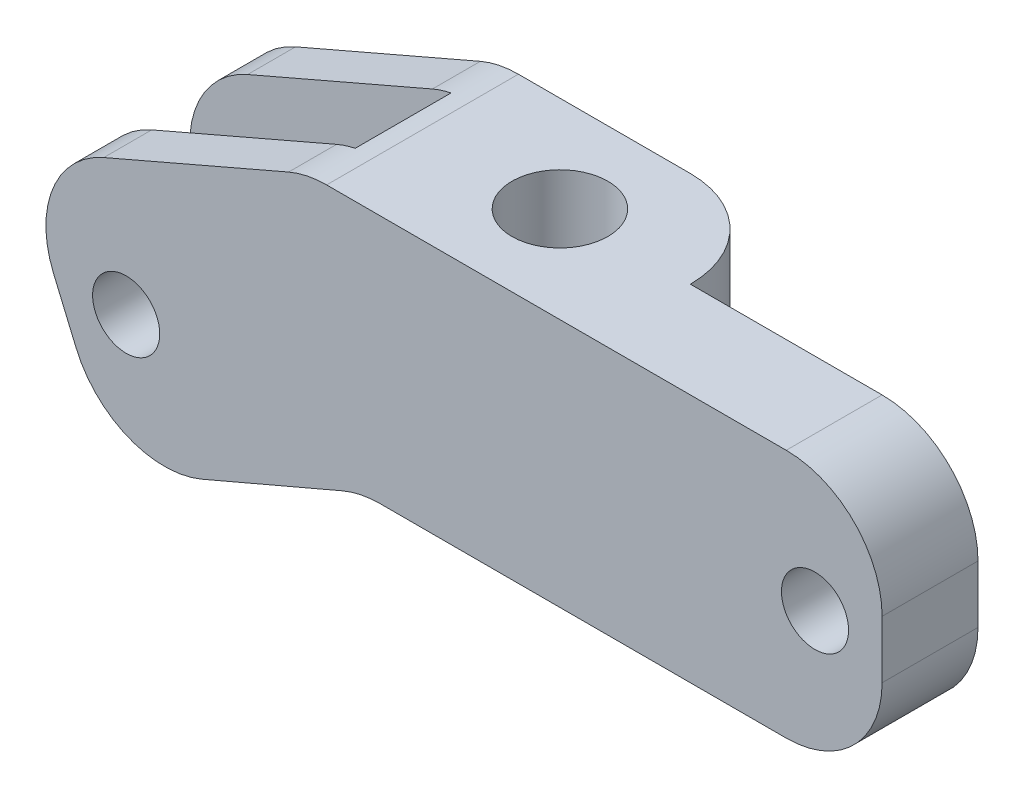
SolidWorks part; units mm, degrees
ref_plane "정면" through (0, 0, 0) normal (0, 0, 1) x (1, 0, 0)
ref_plane "윗면" through (0, 0, 0) normal (0, 1, 0) x (1, 0, 0)
ref_plane "우측면" through (0, 0, 0) normal (1, 0, 0) x (0, 0, -1)
sketch "스케치1" plane through (0, 0, 0) normal (0, 0, 1) x (1, 0, 0)
  line L0 (-6.9042, 6.5443) -> (-22.0507, -0.0005)
  line L1 (-22.0507, -0.0005) -> (-16.9734, -11.9679)
  line L2 (-4.1042, -6.4557) -> (-16.9734, -11.9679)
  line L3 (-4.1042, -6.4557) -> (23.0958, -6.4557)
  line L4 (23.0958, -6.4557) -> (23.0958, 6.5443)
  line L5 (-6.9042, 6.5443) -> (23.0958, 6.5443)
  line L6 (-19.5121, -5.9842) -> (8.0958, 6.5443) construction
  line L7 (23.0958, 0.0443) -> (-21.9471, 0.0443) construction
  circle A0 centre (-16.3239, -4.5374) radius 1.75
  circle A1 centre (19.5958, 0.0443) radius 1.75
  point P0 (-6.9042, 6.5443)
  point P1 (-4.1042, -6.4557)
  point P3 (0.0958, 0.0443)
  dimension "D9" = 3.5
  dimension "D10" = 3.5
  dimension "D1" = 13
  dimension "D2" = 30
  dimension "D3" = 27.2
  dimension "D4" = 16.5
  dimension "D5" = 14
  dimension "D6" = 13
  dimension "D7" = 3.5
  dimension "D8" = 3.5
extrude "보스-돌출1" add sketch "스케치1" along normal blind 10
ref_plane "평면1" through (0, 0, 5) normal (0, 0, 1) x (1, 0, 0)
sketch "스케치5" plane through (0, 0, 5) normal (0, 0, 1) x (1, 0, 0)
  line L0 (-6.9042, 6.5443) -> (23.0958, 6.5443)
  line L1 (23.0958, 6.5443) -> (23.1099, 6.5686)
  line L2 (-19.5121, -5.9842) -> (8.0958, 6.5443) construction
  line L3 (-22.0507, -0.0005) -> (23.0958, 0.0443) construction
  line L4 (8.0958, 6.5443) -> (8.0958, -6.4557)
  line L5 (-6.9042, 6.5443) -> (-4.1042, -6.4557)
  line L8 (-22.0507, -0.0005) -> (-16.9734, -11.9679)
  line L9 (-16.9734, -11.9679) -> (-4.1042, -6.4557)
  line L10 (-4.1042, -6.4557) -> (23.0958, -6.4557)
  line L11 (23.0958, -6.4557) -> (23.0958, 6.5443)
  line L13 (-6.9042, 6.5443) -> (-22.0507, -0.0005)
  circle A0 centre (-16.3239, -4.5374) radius 1.75
  circle A1 centre (19.5958, 0.0443) radius 1.75
  dimension "D1" = 35.9197
sketch "스케치7" plane through (0, 0, 5) normal (0, 0, 1) x (1, 0, 0)
  line L0 (-22.0507, -0.0005) -> (-6.9042, 6.5443)
  line L1 (-6.9042, 6.5443) -> (-4.1042, -6.4557)
  line L2 (-4.1042, -6.4557) -> (-16.9734, -11.9679)
  line L3 (-16.9734, -11.9679) -> (-22.0507, -0.0005)
  line L4 (-22.0507, -0.0005) -> (-22.0505, -0.001)
sketch "스케치8" plane through (0, 0, 5) normal (0, 0, 1) x (1, 0, 0)
  line L0 (-22.0507, -0.0005) -> (-6.9042, 6.5443)
  line L1 (-6.9042, 6.5443) -> (-4.1042, -6.4557)
  line L2 (-4.1042, -6.4557) -> (-16.9734, -11.9679)
  line L3 (-16.9734, -11.9679) -> (-22.0507, -0.0005)
fillet "필렛8" radius 5 6 edges at (-16.9734, -11.9679, 5) (-4.1042, -6.4557, 5) (23.0958, -6.4557, 5) (23.0958, 6.5443, 5) (-22.0507, -0.0005, 5) (-6.9042, 6.5443, 5)
sketch "스케치9" plane through (0, 0, 5) normal (0, 0, 1) x (1, 0, 0)
  line L0 (-22.0507, -0.0005) -> (-6.9042, 6.5443)
  line L1 (-6.9042, 6.5443) -> (-4.1042, -6.4557)
  line L2 (-4.1042, -6.4557) -> (-16.9734, -11.9679)
  line L3 (-16.9734, -11.9679) -> (-22.0507, -0.0005)
extrude "컷-돌출7" cut sketch "스케치9" against normal blind 2.5
sketch "스케치10" plane through (0, 0, 5) normal (0, 0, 1) x (1, 0, 0)
  line L0 (-22.0507, -0.0005) -> (-6.9042, 6.5443)
  line L1 (-6.9042, 6.5443) -> (-4.1042, -6.4557)
  line L2 (-4.1042, -6.4557) -> (-16.9734, -11.9679)
  line L3 (-16.9734, -11.9679) -> (-22.0507, -0.0005)
extrude "컷-돌출8" cut sketch "스케치10" along normal blind 2.5
sketch "스케치11" plane through (0, 0, 5) normal (0, 0, 1) x (1, 0, 0)
  line L0 (8.0958, 6.5443) -> (23.1099, 6.5686)
  line L1 (23.1099, 6.5686) -> (23.0958, -6.4557)
  line L2 (23.0958, -6.4557) -> (8.0958, -6.4557)
  line L3 (8.0958, -6.4557) -> (8.0958, 6.5443)
extrude "컷-돌출9" cut sketch "스케치11" against normal blind 5
fillet "필렛10" radius 5 1 edges at (8.0958, 0.0443, 0)
ref_plane "평면2" through (0, 6.5443, 0) normal (0, 1, 0) x (1, 0, 0)
sketch "스케치12" plane through (0, 6.5443, 0) normal (0, 1, 0) x (1, 0, 0)
  line L0 (-20.5079, 0) -> (-20.5079, -10) construction
  line L1 (-20.5079, -7.5) -> (-20.5079, -10) construction
  line L2 (-20.5079, -10) -> (23.0958, -10) construction
  line L3 (23.0958, -10) -> (23.0958, -5) construction
  line L4 (-4.1042, -5) -> (23.0958, -5) construction
  line L5 (23.0958, -5) -> (23.0958, -10) construction
  line L6 (-20.5079, -5) -> (23.0958, -5) construction
  circle A0 centre (1.2939, -5) radius 2.5
extrude "컷-돌출10" cut sketch "스케치12" against normal blind 10
sketch "스케치13" plane through (0, 0, 5) normal (0, 0, 1) x (1, 0, 0)
